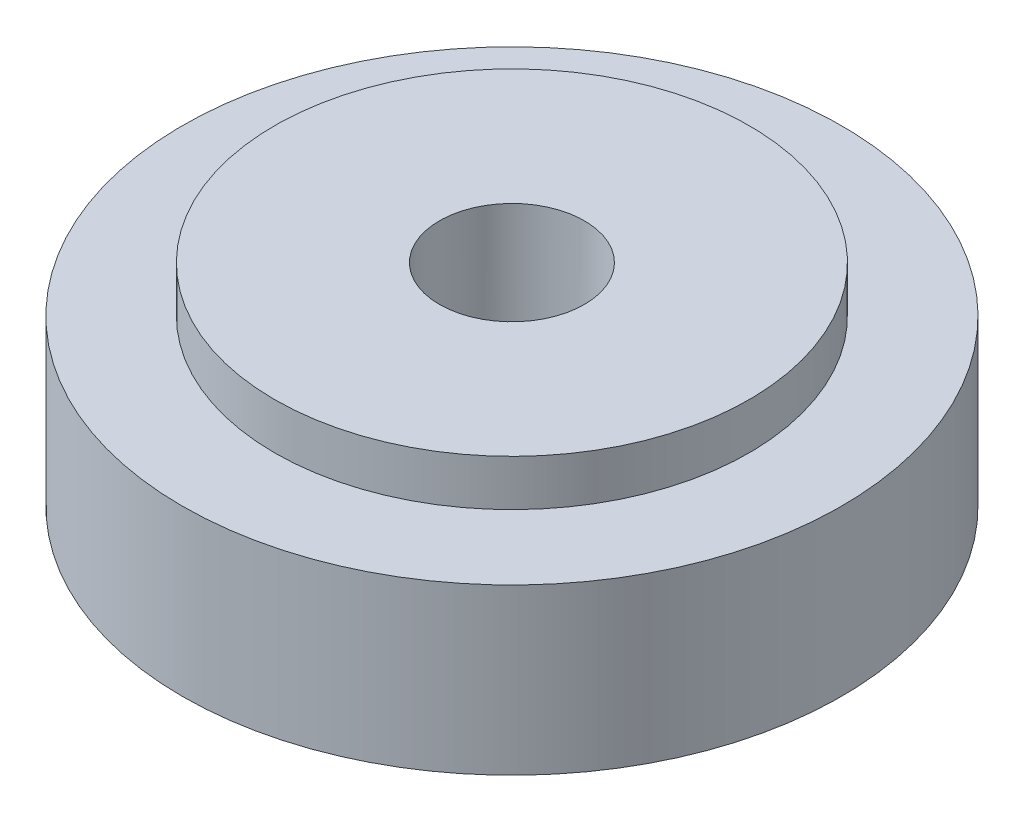
SolidWorks part; units mm, degrees
ref_plane "前视基准面" through (0, 0, 0) normal (0, 0, 1) x (1, 0, 0)
ref_plane "上视基准面" through (0, 0, 0) normal (0, 1, 0) x (1, 0, 0)
ref_plane "右视基准面" through (0, 0, 0) normal (1, 0, 0) x (0, 0, -1)
other "Configuration Table"
sketch "草图1" plane through (0, 0, 0) normal (0, 1, 0) x (1, 0, 0)
  circle A0 centre (0, 0) radius 5
  dimension "D1" = 10
extrude "凸台-拉伸1" add sketch "草图1" along normal blind 2.5
sketch "草图2" plane through (0, 2.5, 0) normal (0, 1, 0) x (1, 0, 0)
  circle A0 centre (0, 0) radius 3.6
  dimension "D1" = 7.2
extrude "凸台-拉伸2" add sketch "草图2" along normal blind 0.7
sketch "草图3" plane through (0, 3.2, 0) normal (0, 1, 0) x (1, 0, 0)
  circle A0 centre (0, 0) radius 1.1
  dimension "D1" = 2.2
extrude "切除-拉伸1" cut sketch "草图3" against normal through all
sketch "草图4" plane through (0, 0, 0) normal (0, -1, 0) x (1, 0, 0)
  circle A0 centre (0, 0) radius 1.9
  dimension "D1" = 3.8
extrude "切除-拉伸2" cut sketch "草图4" against normal blind 1.2
